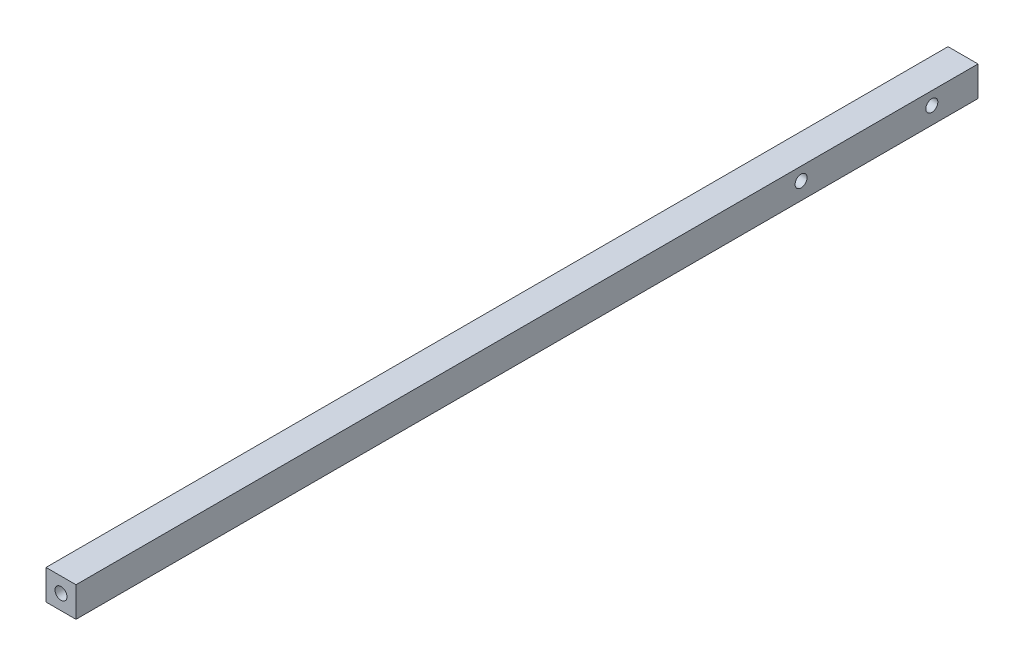
SolidWorks part; units mm, degrees
ref_plane "Plan de face" through (0, 0, 0) normal (0, 0, 1) x (1, 0, 0)
ref_plane "Plan de dessus" through (0, 0, 0) normal (0, 1, 0) x (1, 0, 0)
ref_plane "Plan de droite" through (0, 0, 0) normal (1, 0, 0) x (0, 0, -1)
sketch "Esquisse1" plane through (0, 0, 0) normal (0, 0, 1) x (1, 0, 0)
  line L1 (0, 0) -> (10, 0)
  line L2 (0, 0) -> (0, 10)
  line L3 (0, 10) -> (10, 10)
  line L4 (10, 0) -> (10, 10)
  dimension "D1" = 10
  dimension "D2" = 10
extrude "Boss.-Extru.1" add sketch "Esquisse1" along normal blind 300.81
sketch "Esquisse2" plane through (0, 0, 0) normal (-1, 0, 0) x (0, 0, 1)
  line L0 (63.827, 5.7) -> (-7.5908, 5.7) construction
  line L1 (300.81, 0) -> (0, 0) construction
  line L2 (0, 10) -> (0, 0) construction
  circle A0 centre (15.4, 5.7) radius 2
  circle A1 centre (59, 5.7) radius 2
  dimension "D4" = 4
  dimension "D5" = 4
  dimension "D1" = 5.7
  dimension "D2" = 15.4
  dimension "D3" = 43.6
extrude "Enlèv. mat.-Extru.1" cut sketch "Esquisse2" against normal through all
sketch "Esquisse3" plane through (0, 0, 0) normal (0, 0, -1) x (-1, 0, 0)
  line L0 (0, 10) -> (0, 0) construction
  line L2 (0, 0) -> (-10, 0) construction
  circle A0 centre (-5, 5) radius 2
  dimension "D1" = 4
  dimension "D2" = 5
  dimension "D3" = 5
extrude "Enlèv. mat.-Extru.2" cut sketch "Esquisse3" against normal blind 6
sketch "Esquisse4" plane through (0, 0, 300.81) normal (0, 0, 1) x (1, 0, 0)
  line L0 (0, 10) -> (0, 0) construction
  line L1 (0, 0) -> (10, 0) construction
  circle A0 centre (5, 5) radius 2
  dimension "D1" = 4
  dimension "D2" = 5
  dimension "D3" = 5
extrude "Enlèv. mat.-Extru.3" cut sketch "Esquisse4" against normal blind 6
